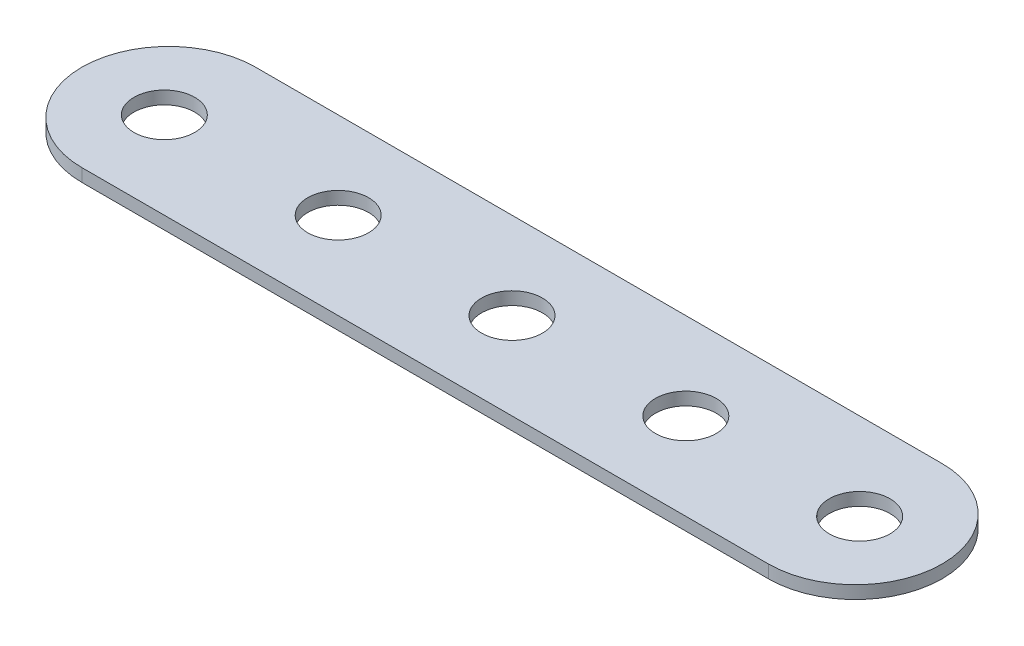
SolidWorks part; units mm, degrees
note: '?' marks a value the reader was unsure of.
ref_plane "Front Plane" through (0, 0, 0) normal (0, 0, 1) x (1, 0, 0)
ref_plane "Top Plane" through (0, 0, 0) normal (0, 1, 0) x (1, 0, 0)
ref_plane "Right Plane" through (0, 0, 0) normal (1, 0, 0) x (0, 0, -1)
ref_plane "Plane1"
sketch "Sketch1" plane through (0, 0, 0) normal (0, 1, 0) x (-1, 0, 0)
  line L0 (50.165, 6.35) -> (0, 6.35)
  line L1 (0, -6.35) -> (50.165, -6.35)
  arc A0 (50.165, -6.35) -> (50.165, 6.35) centre (50.165, 0) ccw
  arc A1 (0, 6.35) -> (0, -6.35) centre (0, 0) ccw
  circle A2 centre (-0.3175, 0) radius 2.2225
  circle A3 centre (50.4825, 0) radius 2.2225
  dimension "D1" = 12.7
  dimension "D3" = 4.445
  dimension "D2" = 50.165
  dimension "D4" = 50.8
extrude "Bar" add sketch "Sketch1" along normal blind 0.9398 contours L0 A1 L1 A0 A3 A2
ref_plane "Plane2" through (0, 0.9398, 0) normal (0, 1, 0) x (1, 0, 0)
sketch "Sketch2" plane through (0, 0.9398, 0) normal (0, 1, 0) x (1, 0, 0)
  circle A0 centre (-37.7825, 0) radius 2.2225
  dimension "D1" = 12.3825
extrude "Center Hole" cut sketch "Sketch2" against normal through all
ref_plane "Plane3" through (0, 0, 0) normal (0, -1, 0) x (-1, 0, 0)
ref_plane "Plane4" through (0, 0, 0) normal (0, 0, 1) x (1, 0, 0)
ref_axis "Axis1" through (-80.9, 0, 0) along (1, 0, 0)?
pattern_linear "Other Center Holes" count 3 spacing 12.7 along (1, 0, 0) of "Center Hole"
